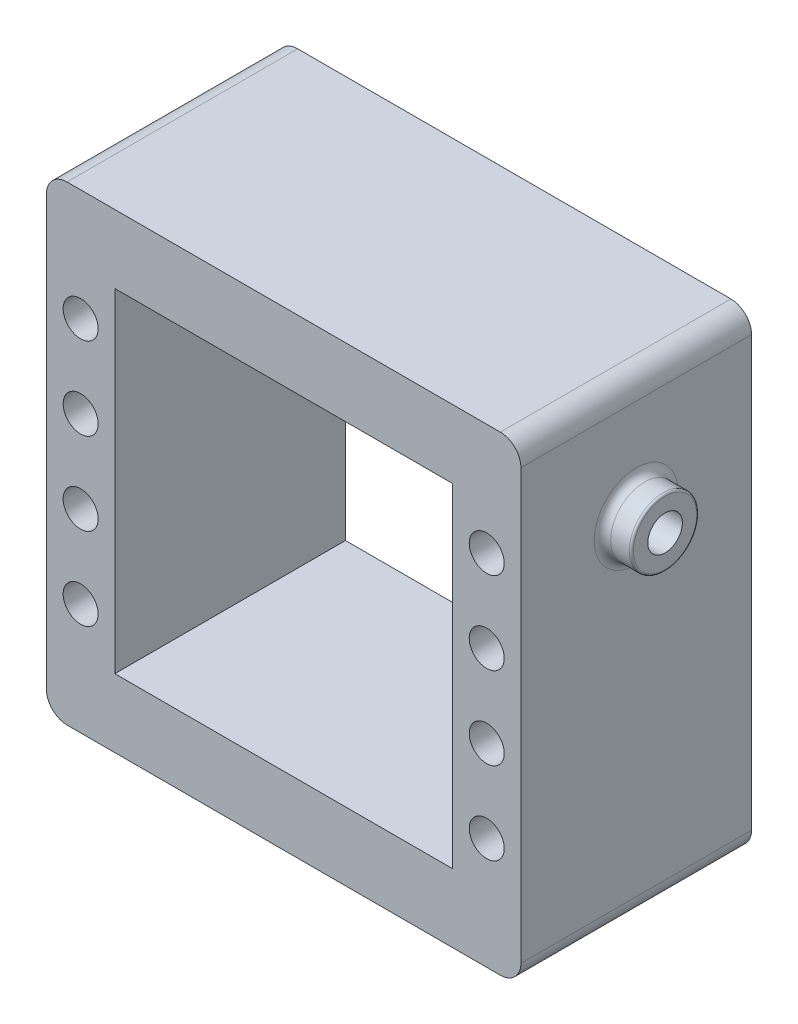
SolidWorks part; units mm, degrees
ref_plane "Front Plane" through (0, 0, 0) normal (0, 0, 1) x (1, 0, 0)
ref_plane "Top Plane" through (0, 0, 0) normal (0, 1, 0) x (1, 0, 0)
ref_plane "Right Plane" through (0, 0, 0) normal (1, 0, 0) x (0, 0, -1)
sketch "Sketch1" plane through (0, 0, 0) normal (0, 0, 1) x (1, 0, 0)
  line L0 (-8.3, -8.3) -> (49.3, -8.3)
  line L1 (0, 0) -> (41, 0)
  line L2 (0, 0) -> (0, 40.5)
  line L3 (0, 40.5) -> (41, 40.5)
  line L4 (41, 0) -> (41, 40.5)
  line L5 (49.3, -8.3) -> (49.3, 48.8)
  line L6 (-8.3, 48.8) -> (49.3, 48.8)
  line L7 (-8.3, -8.3) -> (-8.3, 48.8)
  line L8 (20.5, 48.8) -> (20.5, -8.3) construction
  line L9 (0, 20.25) -> (-8.3, 20.25) construction
  line L10 (-4.15, 20.25) -> (-4.15, 25.25) construction
  line L11 (-4.15, 25.25) -> (-4.15, 35.25) construction
  circle A0 centre (-4.15, 25.25) radius 2.125
  circle A1 centre (-4.15, 35.25) radius 2.125
  circle A2 centre (-4.15, 5.25) radius 2.125
  circle A3 centre (-4.15, 15.25) radius 2.125
  circle A4 centre (45.15, 15.25) radius 2.125
  circle A5 centre (45.15, 5.25) radius 2.125
  circle A6 centre (45.15, 35.25) radius 2.125
  circle A7 centre (45.15, 25.25) radius 2.125
  dimension "D4" = 5
  dimension "D5" = 4.25
  dimension "D1" = 41
  dimension "D2" = 40.5
  dimension "D6" = 10
  dimension "D3" = 8.3
extrude "Boss-Extrude1" add sketch "Sketch1" along normal blind 28
fillet "Fillet1" radius 2.5 4 edges at (49.3, 48.8, 14) (49.3, -8.3, 14) (-8.3, -8.3, 14) (-8.3, 48.8, 14)
sketch "Sketch2" plane through (49.3, 0, 0) normal (-1, 0, 0) x (0, 0, 1)
  line L0 (28, 34.2) -> (0, 34.2) construction
  line L1 (28, 46.3) -> (28, -5.8) construction
  line L2 (0, 46.3) -> (0, -5.8) construction
  line L3 (28, -5.8) -> (0, -5.8) construction
  circle A0 centre (14, 34.2) radius 2.1
  circle A1 centre (14, 34.2) radius 4.1
  point P8 (14, 38.7977)
  dimension "D1" = 4.2
  dimension "D2" = 40
  dimension "D3" = 2
extrude "Boss-Extrude2" add sketch "Sketch2" against normal blind 3.5
fillet "Fillet2" radius 1 1 edges at (49.3, 34.2, 18.1)
fillet "Fillet3" radius 0.25 1 edges at (52.8, 34.2, 18.1)
